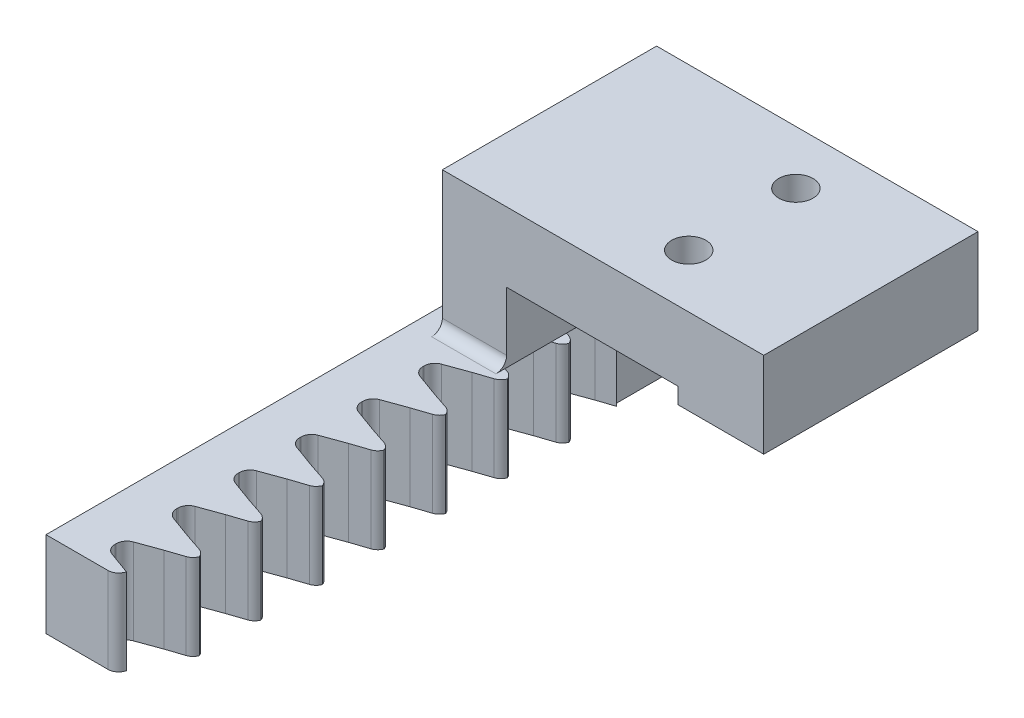
SolidWorks part; units mm, degrees
ref_plane "Front Plane" through (0, 0, 0) normal (0, 0, 1) x (1, 0, 0)
ref_plane "Top Plane" through (0, 0, 0) normal (0, 1, 0) x (1, 0, 0)
ref_plane "Right Plane" through (0, 0, 0) normal (1, 0, 0) x (0, 0, -1)
sketch "Sketch1" plane through (0, 0, 0) normal (0, 0, 1) x (1, 0, 0)
  line L1 (0, 0) -> (30, 0)
  line L2 (0, 0) -> (0, -16)
  line L3 (0, -16) -> (30, -16)
  line L4 (30, 0) -> (30, -16)
  dimension "D1" = 30
  dimension "D2" = 16
extrude "Boss-Extrude1" add sketch "Sketch1" along normal blind 20
sketch "Sketch2" plane through (0, 0, 20) normal (0, 0, 1) x (1, 0, 0)
  line L0 (22, -6.5) -> (22, -8)
  line L7 (6, -16) -> (6, -6.5)
  line L8 (6, -6.5) -> (22, -6.5)
  line L14 (22, -8) -> (30, -8)
  line L15 (30, -16) -> (30, 0) construction
  line L16 (30, -8) -> (30, -16)
  line L17 (30, -16) -> (6, -16)
  dimension "D1" = 24
  dimension "D2" = 8
  dimension "D7" = 16
extrude "Cut-Extrude1" cut sketch "Sketch2" against normal up to surface (20 mm away) contours L8 L0 L14 L16 L17 L7 up to face at (15, -8, 0)
sketch "Sketch3" plane through (0, -16, 0) normal (0, -1, 0) x (1, 0, 0)
  line L0 (0, 20) -> (0, 0) construction
  line L1 (0, 15) -> (6, 15)
  line L2 (0, 15) -> (0, 5)
  line L3 (0, 5) -> (6, 5)
  line L4 (6, 15) -> (6, 5)
  line L6 (0, 20) -> (6, 20) construction
  dimension "D1" = 5
  dimension "D2" = 10
  dimension "D3" = 6
extrude "Boss-Extrude2" add sketch "Sketch3" along normal blind 5
ref_plane "Plane1" through (0, 0, 0) normal (-1, 0, 0) x (0, 0, 1)
sketch "Sketch9" plane through (0, -6.5, 0) normal (0, -1, 0) x (1, 0, 0)
  line L0 (30, 0) -> (30, 20) construction
  line L3 (6, 20) -> (22, 20) construction
  circle A0 centre (18, 15) radius 1.6
  circle A1 centre (18, 5) radius 1.6
  dimension "D1" = 3.2
  dimension "D2" = 3.2
  dimension "D3" = 12
  dimension "D4" = 12
  dimension "D5" = 10
  dimension "D6" = 5
extrude "Cut-Extrude3" cut sketch "Sketch9" against normal up to surface (6.5 mm away) up to face at (15, 0, 10)
sketch "Sketch11" plane through (0, 0, 15) normal (0, 0, 1) x (1, 0, 0)
  line L0 (6, -21) -> (0, -21) construction
  line L1 (-2, -13) -> (8, -13)
  line L2 (-2, -13) -> (-2, -21)
  line L3 (-2, -21) -> (8, -21)
  line L4 (8, -13) -> (8, -21)
  line L5 (0, -21) -> (0, -16) construction
  line L6 (6, -21) -> (6, -16) construction
  dimension "D1" = 2
  dimension "D2" = 2
  dimension "D3" = 8
extrude "Boss-Extrude4" add sketch "Sketch11" along normal blind 40
chamfer "Chamfer2" distance 2 distance2 10 1 edges first distance on face at (-1, -18, 15)
fillet "Fillet1" radius 1 1 edges at (3, -13, 20)
sketch "Sketch12" plane through (0, -21, 0) normal (0, -1, 0) x (1, 0, 0)
  line L0 (7, 55) -> (4.75, 54.25)
  line L1 (4.75, 54.25) -> (2, 53.25)
  line L3 (2, 52.5) -> (8, 52.5) construction
  line L4 (8, 55) -> (8, 15) construction
  line L7 (2, 55) -> (2, 48) construction
  line L8 (-2, 55) -> (8, 55) construction
  line L14 (2, 53.25) -> (2, 51.75)
  line L15 (4.75, 50.75) -> (2, 51.75)
  line L16 (7, 50) -> (4.75, 50.75)
  line L17 (7, 55) -> (8, 55)
  line L18 (7, 50) -> (7, 49.25)
  line L19 (7, 49.25) -> (8, 49.25)
  line L20 (8, 49.25) -> (8, 55)
  dimension "D1" = 0.75
  dimension "D2" = 1
  dimension "D3" = 2.25
  dimension "D4" = 1
  dimension "D5" = 0.75
  dimension "D6" = 6
  dimension "D7" = 0.75
extrude "Cut-Extrude4" cut sketch "Sketch12" against normal blind 8
sketch "Sketch13" plane through (0, 0, 15) normal (0, 0, -1) x (-1, 0, 0)
  line L0 (-6, -21) -> (-8, -21) construction
  line L1 (-8, -13) -> (-6, -13)
  line L2 (-8, -13) -> (-8, -21)
  line L3 (-8, -21) -> (-6, -21)
  line L4 (-6, -13) -> (-6, -21)
extrude "Boss-Extrude5" add sketch "Sketch13" along normal blind 10
pattern_linear "LPattern1" count 8 spacing 5.75 along (0, 0, -1) of "Cut-Extrude4"
fillet "Fillet2" radius 1 30 edges at (2, -17, 51.75) (2, -17, 53.25) (2, -17, 46) (2, -17, 47.5) (2, -17, 40.25) (2, -17, 41.75) (2, -17, 28.75) (2, -17, 30.25) (2, -17, 34.5) (2, -17, 36) (7, -17, 26.25) (7, -17, 27) (7, -17, 32) (7, -17, 32.75) (7, -17, 37.75) (7, -17, 38.5) (7, -17, 43.5) (7, -17, 44.25) (7, -17, 49.25) (7, -17, 50) (7, -17, 14.75) (7, -17, 15.5) (7, -17, 20.5) (7, -17, 21.25) (2, -17, 11.5) (2, -17, 13) (2, -17, 17.25) (2, -17, 18.75) (2, -17, 24.5) (2, -17, 23)
fillet "Fillet3" radius 1 1 edges at (7, -17, 55)
sketch "Sketch14" plane through (0, 0, 5) normal (0, 0, -1) x (-1, 0, 0)
  line L1 (-6, -13) -> (-8, -13)
  line L2 (-6, -13) -> (-6, -21)
  line L3 (-6, -21) -> (-8, -21)
  line L4 (-8, -13) -> (-8, -21)
extrude "Cut-Extrude5" cut sketch "Sketch14" against normal blind 5
